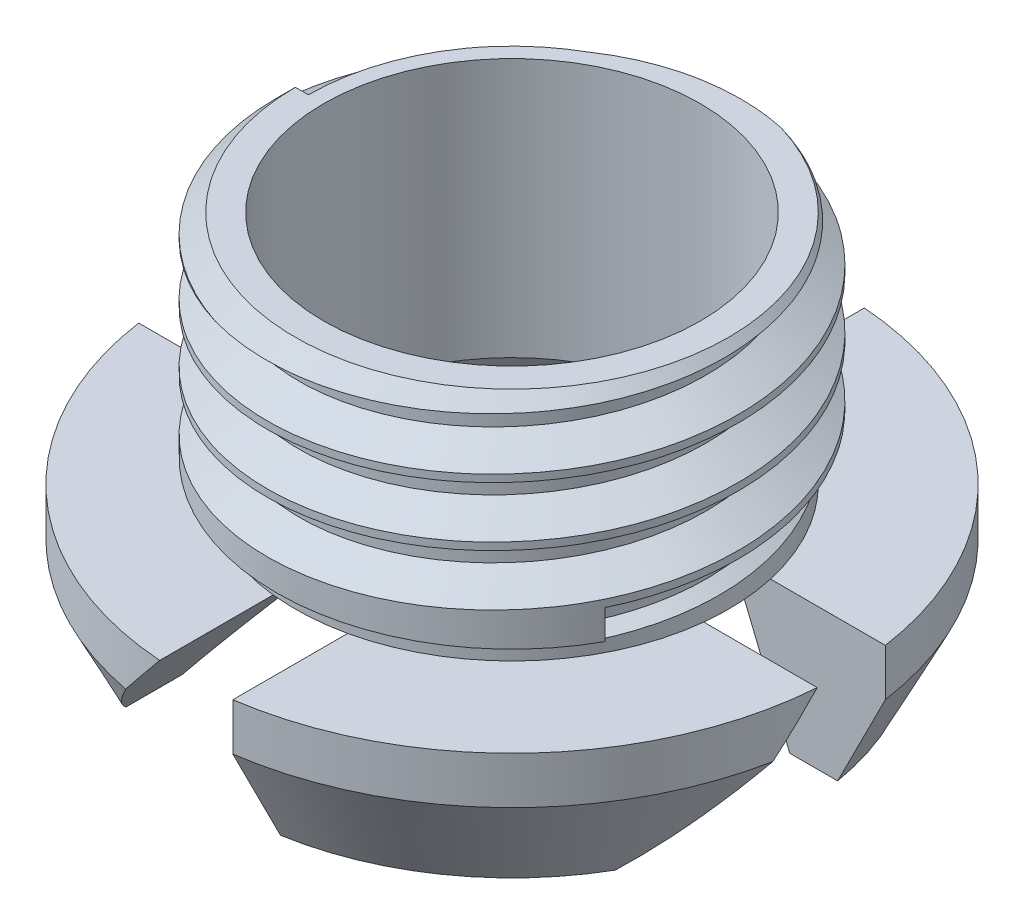
SolidWorks part; units mm, degrees
ref_plane "前视基准面" through (0, 0, 0) normal (0, 0, 1) x (1, 0, 0)
ref_plane "上视基准面" through (0, 0, 0) normal (0, 1, 0) x (1, 0, 0)
ref_plane "右视基准面" through (0, 0, 0) normal (1, 0, 0) x (0, 0, -1)
other "Configuration Table"
sketch "草图3" plane through (0, 0, 0) normal (0, 0, 1) x (1, 0, 0)
  line L0 (0, 34.5575) -> (0, -28.0088) construction
  line L1 (8, 5.5) -> (10, 5.5)
  line L2 (10, 5.5) -> (10, -4.5)
  line L3 (10, -4.5) -> (14, -4.5)
  line L4 (14, -4.5) -> (14, -6.5)
  line L5 (14, -6.5) -> (12, -10.5)
  line L6 (12, -10.5) -> (10, -10.5)
  line L7 (10, -10.5) -> (8, -5.5)
  line L8 (8, -5.5) -> (8, 5.5)
  point P14 (8, 0)
  dimension "D1" = 20
  dimension "D2" = 16
  dimension "D3" = 10
  dimension "D4" = 6
  dimension "D5" = 28
  dimension "D6" = 2
  dimension "D7" = 20
  dimension "D8" = 2
  dimension "D9" = 5
revolve "旋转1" add sketch "草图3" angle 360 about L0
cosmetic thread "装饰螺纹线1" parameters "D2"=17.294
sketch "草图4" plane through (0, 0, 0) normal (0, 0, 1) x (1, 0, 0)
  line L0 (0, 6.7757) -> (0, -14.1887) construction
  line L1 (10, -4.5) -> (9.2, -4.5)
  line L2 (14, -4.5) -> (-14, -4.5) construction
  line L3 (9.2, -4.5) -> (9.2, -3.5)
  line L4 (9.2, -3.5) -> (10, -3.5)
  line L5 (10, -4.5) -> (10, 5.5) construction
  line L6 (10, -3.5) -> (10, -4.5)
  dimension "D1" = 0.8
  dimension "D2" = 1
revolve "切除-旋转1" cut sketch "草图4" angle 360 about L0
chamfer "倒角1" distance 0.8 angle 45 1 edges at (0, 5.5, 10)
sketch "草图5" plane through (0, 0, 0) normal (0, 0, 1) x (1, 0, 0)
  line L0 (0, 12.9366) -> (0, -22.1886) construction
  line L1 (-1, -4.5) -> (2, -4.5)
  line L2 (14, -4.5) -> (-14, -4.5) construction
  line L3 (2, -4.5) -> (2, -10.5)
  line L4 (-12, -10.5) -> (12, -10.5) construction
  line L5 (2, -10.5) -> (-6, -10.5)
  line L6 (-6, -10.5) -> (-1, -4.5)
  dimension "D1" = 3
  dimension "D2" = 8
  dimension "D3" = 2
extrude "切除-拉伸1" cut sketch "草图5" along normal up to next
pattern_circular "阵列(圆周)1" count 4 over 360 about axis through (0, 0, 0) along (0, 1, 0) of "切除-拉伸1"
thread "螺纹线1" pitch 2.5 start angle 0, offset 2, length 0, pitch 2.5, diameter 20
ref_plane "基准面1" through (-10, 6.7, 0) normal (0, 0, 1) x (-1, 0, 0)
sketch "螺纹线轮廓1" plane through (-10, 6.7, 0) normal (0, 0, 1) x (-1, 0, 0)
  line L0 (0, 0) -> (0, 2.5) construction
  line L11 (0, 0) -> (0, 2.1875)
  line L12 (0, 2.1875) -> (-1.3532, 1.4062)
  line L13 (-1.3532, 1.4062) -> (-1.3532, 0.7812)
  line L15 (-1.3532, 0.7812) -> (0, 0)
  line L17 (-1.3532, 1.0937) -> (0, 1.0937) construction
  point P2 (0, 0)
  dimension "Pitch" = 2.5
  dimension "Profile_Angle" = 60
  dimension "Profile_Land" = 0.625
  dimension "Profile_Height" = 1.3532
